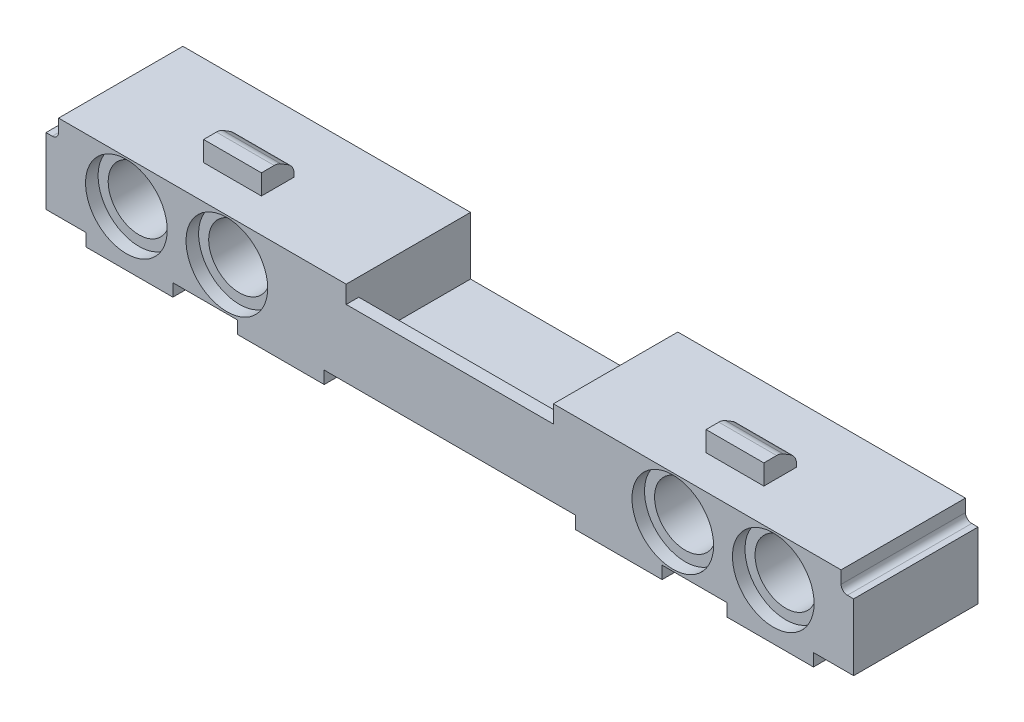
SolidWorks part; units mm, degrees
ref_plane "Front Plane" through (0, 0, 0) normal (0, 0, 1) x (1, 0, 0)
ref_plane "Top Plane" through (0, 0, 0) normal (0, 1, 0) x (1, 0, 0)
ref_plane "Right Plane" through (0, 0, 0) normal (1, 0, 0) x (0, 0, -1)
sketch "Sketch1" plane through (0, 0, 0) normal (0, 0, 1) x (1, 0, 0)
  line L0 (-32.35, -3.6) -> (-32.35, 3.6)
  line L1 (-32.15, -3.4) -> (32.15, -3.4)
  line L2 (-32.15, -3.4) -> (-32.15, 3.4)
  line L3 (-32.15, 3.4) -> (32.15, 3.4)
  line L4 (32.15, -3.4) -> (32.15, 3.4)
  line L5 (-32.15, -3.4) -> (32.15, 3.4) construction
  line L6 (-32.15, 3.4) -> (32.15, -3.4) construction
  line L7 (-32.35, 3.6) -> (32.35, 3.6)
  line L8 (32.35, -3.6) -> (32.35, 3.6)
  line L9 (-32.35, -3.6) -> (32.35, -3.6)
  line L10 (-9.75, 0) -> (9.75, 0)
  line L11 (-9.75, 0) -> (-17.75, 0)
  line L12 (0, 0) -> (0, 2.5241)
  line L13 (-17.75, 0) -> (-25.75, 0)
  line L14 (9.75, 0) -> (17.75, 0)
  line L15 (17.75, 0) -> (25.75, 0)
  circle A1 centre (-17.75, 0) radius 2.45
  circle A2 centre (-25.75, 0) radius 2.45
  circle A4 centre (17.75, 0) radius 2.45
  circle A5 centre (25.75, 0) radius 2.45
  point P0 (0, 0)
  point P13 (0, 0)
  dimension "D7" = 4.9
  dimension "D8" = 4.9
  dimension "D1" = 64.3
  dimension "D2" = 6.8
  dimension "D4" = 19.5
  dimension "D6" = 8
  dimension "D9" = 8
  dimension "D3" = 0.2
extrude "Boss-Extrude2" add sketch "Sketch1" along normal blind 9.9 contours L1 L4 L3 L2 A5 A4 A1 A2 region at (-31.5034, 0, 0)
sketch "Sketch2" plane through (0, 0, 0) normal (0, 0, -1) x (-1, 0, 0)
  line L0 (0, 0) -> (0, -2.1714)
  circle A0 centre (-25.75, 0) radius 3.25
  circle A1 centre (-17.75, 0) radius 3.25
  circle A4 centre (17.75, 0) radius 3.25
  circle A5 centre (25.75, 0) radius 3.25
  dimension "D1" = 6.5
  dimension "D2" = 6.5
extrude "Cut-Extrude1" cut sketch "Sketch2" against normal blind 2.9 contours A1 | A0 | A4 | A5
sketch "Sketch5" plane through (0, 0, 9.9) normal (0, 0, 1) x (1, 0, 0)
  line L0 (0, 3.4) -> (0, 7.0243)
  line L1 (-32.15, 3.4) -> (-31.15, 3.4)
  line L2 (-32.15, 3.4) -> (-32.15, 1.9)
  line L3 (-32.15, 1.9) -> (-31.65, 1.9)
  line L4 (-31.15, 3.4) -> (-31.15, 2.4)
  line L5 (-32.15, 3.4) -> (32.15, 3.4) construction
  line L6 (31.15, 3.4) -> (31.15, 2.4)
  line L7 (32.15, 1.9) -> (31.65, 1.9)
  line L8 (32.15, 3.4) -> (32.15, 1.9)
  line L9 (32.15, 3.4) -> (31.15, 3.4)
  arc A0 (-31.15, 2.4) -> (-31.65, 1.9) centre (-31.65, 2.4) cw
  arc A1 (31.15, 2.4) -> (31.65, 1.9) centre (31.65, 2.4) ccw
  line M12 (32.15, -3.4) -> (32.15, 3.4)
  line M13 (32.15, 3.4) -> (-32.15, 3.4)
  dimension "D3" = 0.5
  dimension "D1" = 1
  dimension "D2" = 1.5
extrude "Cut-Extrude2" cut sketch "Sketch5" against normal blind 11 contours L6 A1 L7 M12 M13 | L2 L3 A0 L4 L1 region at (31.6644, 2.6737, 9.9)
sketch "Sketch7" plane through (0, 0, 9.9) normal (0, 0, 1) x (1, 0, 0)
  line L0 (-32.15, -3.4) -> (-28.95, -3.4)
  line L1 (-32.15, -3.4) -> (32.15, -3.4) construction
  line L2 (-22.05, -3.4) -> (-16.9, -3.4)
  line L3 (-28.95, -3.4) -> (-22.05, -3.4)
  line L4 (-28.95, -3.4) -> (-28.95, -4.4)
  line L5 (-28.95, -4.4) -> (-22.05, -4.4)
  line L6 (-22.05, -3.4) -> (-22.05, -4.4)
  line L7 (0, 0) -> (0, 6.5242)
  line L8 (-16.9, -3.4) -> (-10, -3.4)
  line L9 (-16.9, -3.4) -> (-16.9, -4.4)
  line L10 (-16.9, -4.4) -> (-10, -4.4)
  line L11 (-10, -3.4) -> (-10, -4.4)
  line L12 (10, -3.4) -> (10, -4.4)
  line L13 (16.9, -4.4) -> (10, -4.4)
  line L14 (16.9, -3.4) -> (16.9, -4.4)
  line L15 (16.9, -3.4) -> (10, -3.4)
  line L16 (22.05, -3.4) -> (22.05, -4.4)
  line L17 (28.95, -4.4) -> (22.05, -4.4)
  line L18 (28.95, -3.4) -> (28.95, -4.4)
  line L19 (28.95, -3.4) -> (22.05, -3.4)
  line L20 (22.05, -3.4) -> (16.9, -3.4)
  line L21 (32.15, -3.4) -> (28.95, -3.4)
  line M13 (-32.15, -3.4) -> (32.15, -3.4)
  dimension "D1" = 3.2
  dimension "D2" = 6.9
  dimension "D3" = 1
  dimension "D4" = 1
  dimension "D5" = 6.9
  dimension "D6" = 5.15
extrude "Boss-Extrude3" add sketch "Sketch7" against normal up to surface (9.9 mm away) contours L6 L4 L5 M13 | L11 L9 L10 M13 | L14 L12 L13 M13 | L18 L16 L17 M13 region at (25.5, -3.9, 9.9) region at (13.45, -3.9, 9.9) region at (-13.45, -3.9, 9.9) region at (-25.5, -3.9, 9.9) up to face at (-22.5, 0, 0)
sketch "Sketch8" plane through (0, 0, 9.9) normal (0, 0, 1) x (1, 0, 0)
  line L0 (-31.15, 3.4) -> (31.15, 3.4) construction
  line L1 (-8.25, 6.4) -> (8.25, 6.4)
  line L2 (-8.25, 6.4) -> (-8.25, 0.4)
  line L3 (-8.25, 0.4) -> (8.25, 0.4)
  line L4 (8.25, 6.4) -> (8.25, 0.4)
  line L5 (-8.25, 6.4) -> (8.25, 0.4) construction
  line L6 (-8.25, 0.4) -> (8.25, 6.4) construction
  point P0 (0, 3.4)
  dimension "D1" = 16.5
  dimension "D2" = 6
extrude "Cut-Extrude3" cut sketch "Sketch8" against normal blind 12
sketch "Sketch9" plane through (0, 0, 9.9) normal (0, 0, 1) x (1, 0, 0)
  line L0 (8.25, 0.4) -> (8.25, 3.4) construction
  line L1 (-8.25, 0.4) -> (8.25, 0.4)
  line L2 (-8.25, 0.4) -> (-8.25, 2)
  line L3 (-8.25, 2) -> (8.25, 2)
  line L4 (8.25, 0.4) -> (8.25, 2)
  dimension "D1" = 1.6
extrude "Boss-Extrude4" add sketch "Sketch9" against normal blind 1 contours L2 L1 L4 L3
sketch "Sketch10" plane through (0, 3.4, 0) normal (0, 1, 0) x (1, 0, 0)
  line L0 (0, -9.9) -> (0, -5.9)
  line L1 (-8.25, -9.9) -> (8.25, -9.9) construction
  line L2 (-20, -5.9) -> (20, -5.9)
  line L4 (-22.3, -7.2) -> (-17.7, -7.2)
  line L5 (-22.3, -7.2) -> (-22.3, -4.6)
  line L6 (-22.3, -4.6) -> (-17.7, -4.6)
  line L7 (-17.7, -7.2) -> (-17.7, -4.6)
  line L8 (-22.3, -7.2) -> (-17.7, -4.6) construction
  line L9 (-22.3, -4.6) -> (-17.7, -7.2) construction
  line L10 (17.7, -7.2) -> (22.3, -7.2)
  line L11 (17.7, -7.2) -> (17.7, -4.6)
  line L12 (17.7, -4.6) -> (22.3, -4.6)
  line L13 (22.3, -7.2) -> (22.3, -4.6)
  line L14 (17.7, -7.2) -> (22.3, -4.6) construction
  line L15 (17.7, -4.6) -> (22.3, -7.2) construction
  point P8 (0, -5.9)
  dimension "D1" = 40
  dimension "D2" = 4.6
  dimension "D3" = 2.6
  dimension "D4" = 4.6
  dimension "D5" = 2.6
  dimension "D6" = 4
extrude "Boss-Extrude5" add sketch "Sketch10" along normal blind 1.6 contours L6 L7 L4 L5 | L12 L13 L10 L11
sketch "Sketch11" plane through (-22.3, 0, 0) normal (-1, 0, 0) x (0, 0, 1)
  line L0 (5.9, 5) -> (4.6, 4.2)
  line L2 (7.2, 5) -> (4.6, 5) construction
  line L4 (4.6, 5) -> (4.6, 3.4) construction
  line L5 (4.6, 4.2) -> (7.2, 4.2)
  line L6 (7.2, 5) -> (7.2, 3.4) construction
  line L7 (7.2, 4.2) -> (7.2, 5)
  line L8 (7.2, 5) -> (5.9, 5)
  line L9 (4.6, 4.2) -> (4.6, 5)
  line L10 (4.6, 5) -> (5.9, 5)
  line M3 (7.2, 5) -> (4.6, 5)
  line M4 (4.6, 5) -> (4.6, 3.4)
extrude "Cut-Extrude4" cut sketch "Sketch11" against normal up to surface (44.6 mm away) contours L0 M3 M4 region at (-22.3, 4.7333, 5.0333) up to face at (22.3, 4.2, 5.9)
fillet "Fillet1" radius 1 4 edges at (20, 4.2, 4.6) (-20, 4.2, 4.6) (-20, 5, 5.9) (20, 5, 5.9)
sketch "Sketch13" plane through (0, 0, 9.9) normal (0, 0, 1) x (1, 0, 0)
  circle A0 centre (-25.75, 0) radius 3.25
  circle A1 centre (-17.75, 0) radius 3.25
  circle A2 centre (25.75, 0) radius 3.25
  circle A3 centre (17.75, 0) radius 3.25
  dimension "D1" = 6.5
  dimension "D2" = 6.5
  dimension "D3" = 6.5
  dimension "D4" = 6.5
extrude "Cut-Extrude6" cut sketch "Sketch13" against normal blind 1 contours A0 | A1 | A3 | A2
sketch "Sketch14" plane through (0, 0.4, 0) normal (0, 1, 0) x (1, 0, 0)
  line L1 (8.25, 0) -> (-8.25, 0)
  line L2 (8.25, 0) -> (8.25, -8.9)
  line L3 (8.25, -8.9) -> (-8.25, -8.9)
  line L4 (-8.25, 0) -> (-8.25, -8.9)
extrude "Cut-Extrude7" cut sketch "Sketch14" against normal blind 1.6
